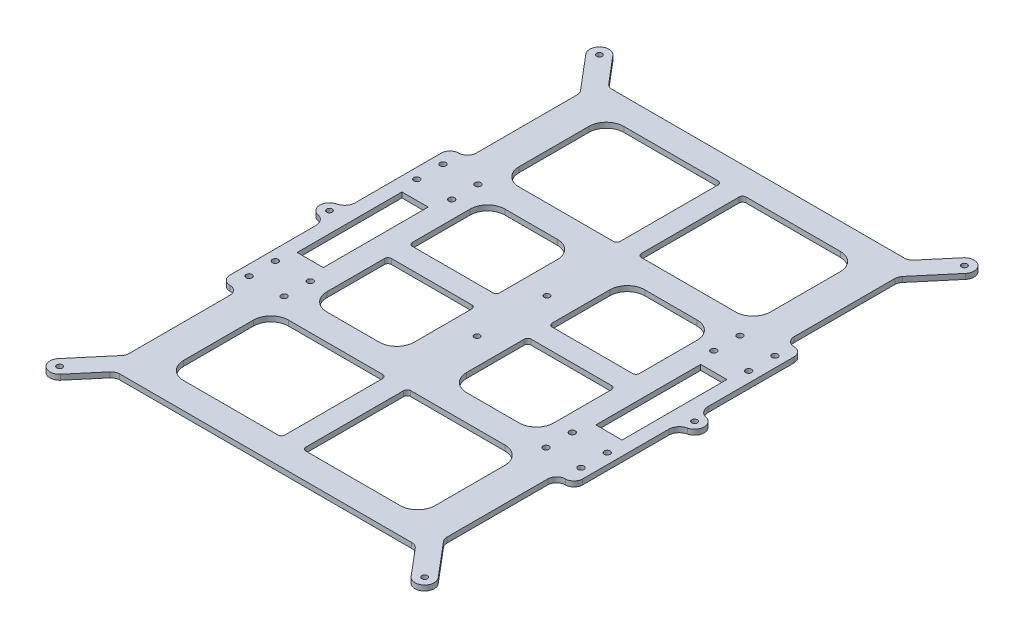
SolidWorks part; units mm, degrees
material "Aleación 1060"
ref_plane "Alzado" through (0, 0, 0) normal (0, 0, 1) x (1, 0, 0)
ref_plane "Planta" through (0, 0, 0) normal (0, 1, 0) x (1, 0, 0)
ref_plane "Vista lateral" through (0, 0, 0) normal (1, 0, 0) x (0, 0, -1)
sketch "Croquis1" plane through (0, 0, 0) normal (0, 1, 0) x (1, 0, 0)
  line L0 (110, 320) -> (110, 0) construction
  line L1 (0, 0) -> (220, 0)
  line L2 (0, 0) -> (0, 320)
  line L3 (0, 320) -> (220, 320)
  line L4 (220, 0) -> (220, 320)
  line L5 (0, 160) -> (220, 160) construction
  line L6 (19, 320) -> (19, 0) construction
  line L7 (31, 320) -> (31, 0) construction
  line L8 (189, 320) -> (189, 0) construction
  line L9 (201, 320) -> (201, 0) construction
  line L10 (195, 320) -> (195, 0) construction
  line L11 (25, 320) -> (25, 0) construction
  line L12 (5.5, 314.5) -> (5.5, 160) construction
  circle A7 centre (35, 215.5) radius 1.7
  circle A8 centre (35, 200.5) radius 1.7
  circle A10 centre (35, 119.5) radius 1.7
  circle A13 centre (35, 104.5) radius 1.7
  circle A14 centre (5.5, 314.5) radius 1.6
  circle A15 centre (214.5, 314.5) radius 1.6
  circle A16 centre (214.5, 5.5) radius 1.6
  circle A17 centre (5.5, 5.5) radius 1.6
  circle A18 centre (15, 200.5) radius 1.7
  circle A19 centre (15, 215.5) radius 1.7
  circle A20 centre (15, 104.5) radius 1.7
  circle A21 centre (15, 119.5) radius 1.7
  circle A22 centre (110, 180) radius 1.6
  circle A23 centre (110, 140) radius 1.6
  circle A32 centre (5.5, 160) radius 1.6
  circle A37 centre (214.5, 160) radius 1.6
  circle A38 centre (185, 104.5) radius 1.7
  circle A39 centre (185, 119.5) radius 1.7
  circle A40 centre (205, 119.5) radius 1.7
  circle A41 centre (205, 104.5) radius 1.7
  circle A42 centre (185, 215.5) radius 1.7
  circle A43 centre (185, 200.5) radius 1.7
  circle A44 centre (205, 200.5) radius 1.7
  circle A45 centre (205, 215.5) radius 1.7
  dimension "D13" = 6
  dimension "D14" = 3.4
  dimension "D17" = 3.2
  dimension "D23" = 3.2
  dimension "D18" = 20
  dimension "D1" = 320
  dimension "D2" = 220
  dimension "D3" = 12
  dimension "D4" = 12
  dimension "D5" = 158
  dimension "D6" = 19
  dimension "D7" = 6
  dimension "D15" = 10
  dimension "D16" = 15
  dimension "D20" = 10
  dimension "D21" = 104.5
  dimension "D24" = 5.5
  dimension "D25" = 5.5
extrude "Saliente-Extruir1" add sketch "Croquis1" along normal blind 3
sketch "Croquis2" plane through (0, 3, 0) normal (0, 1, 0) x (1, 0, 0)
  line L0 (220, 160) -> (0, 160) construction
  line L2 (9, 9) -> (211, 9) construction
  line L3 (220, 0) -> (220, 320) construction
  line L4 (9, 148.775) -> (9, 94.5)
  line L5 (110, 320) -> (110, 0) construction
  line L6 (220, 320) -> (0, 320) construction
  line L7 (0, 0) -> (220, 0) construction
  line L8 (9, 9) -> (211, 9)
  line L9 (211, 9) -> (211, 311)
  line L10 (211, 311) -> (9, 311)
  line L11 (9, 311) -> (9, 9)
  line L15 (9, 225.5) -> (9, 171.225)
  line L16 (9, 225.5) -> (19, 225.5)
  line L18 (19, 94.5) -> (9, 94.5)
  line L19 (19, 94.5) -> (19, 30)
  line L20 (24.1066, 19) -> (195.8934, 19)
  line L21 (210.2988, 1.9504) -> (195.8934, 19)
  line L22 (1.2988, 9.0496) -> (19, 30)
  line L23 (9.7012, 1.9504) -> (24.1066, 19)
  line L24 (9, 148.775) -> (9, 9) construction
  line L25 (19, 148.775) -> (19, 19) construction
  line L26 (19, 19) -> (201, 19) construction
  line L27 (211, 9) -> (211, 311) construction
  line L28 (19, 225.5) -> (19, 290)
  line L29 (24.1066, 301) -> (195.8934, 301)
  line L30 (1.2988, 310.9504) -> (19, 290)
  line L31 (9.7012, 318.0496) -> (24.1066, 301)
  line L32 (0, 320) -> (0, 0) construction
  line L33 (218.7012, 9.0496) -> (201, 30)
  line L34 (201, 19) -> (201, 311) construction
  line L35 (201, 94.5) -> (201, 30)
  line L36 (201, 94.5) -> (211, 94.5)
  line L37 (211, 148.775) -> (211, 94.5)
  line L38 (211, 225.5) -> (211, 171.225)
  line L39 (211, 225.5) -> (201, 225.5)
  line L40 (201, 225.5) -> (201, 290)
  line L41 (218.7012, 310.9504) -> (201, 290)
  line L42 (210.2988, 318.0496) -> (195.8934, 301)
  line L43 (182, 276) -> (182, 236)
  line L44 (102, 286) -> (48, 286)
  line L46 (102, 226) -> (48, 226)
  line L47 (38, 276) -> (38, 236)
  line L48 (118, 226) -> (172, 226)
  line L52 (104, 284) -> (104, 228)
  line L53 (116, 284) -> (116, 228)
  line L54 (118, 286) -> (172, 286)
  line L55 (102, 94) -> (48, 94)
  line L56 (38, 44) -> (38, 84)
  line L57 (102, 34) -> (48, 34)
  line L58 (104, 36) -> (104, 92)
  line L59 (116, 36) -> (116, 92)
  line L60 (118, 34) -> (172, 34)
  line L61 (182, 44) -> (182, 84)
  line L62 (118, 94) -> (172, 94)
  line L63 (45, 152) -> (45, 119)
  line L64 (93, 166) -> (47, 166)
  line L65 (95, 168) -> (95, 201)
  line L66 (85, 211) -> (55, 211)
  line L67 (45, 168) -> (45, 201)
  line L68 (85, 109) -> (55, 109)
  line L69 (95, 152) -> (95, 119)
  line L70 (93, 154) -> (47, 154)
  line L71 (135, 109) -> (165, 109)
  line L72 (175, 152) -> (175, 119)
  line L73 (125, 152) -> (125, 119)
  line L74 (127, 154) -> (173, 154)
  line L75 (127, 166) -> (173, 166)
  line L76 (175, 168) -> (175, 201)
  line L77 (135, 211) -> (165, 211)
  line L78 (125, 168) -> (125, 201)
  arc A2 (1.2988, 9.0496) -> (9.7012, 1.9504) centre (5.5, 5.5) ccw
  arc A3 (4.3043, 165.3685) -> (4.3043, 154.6315) centre (5.5, 160) ccw
  arc A4 (9, 148.775) -> (4.3043, 154.6315) centre (3, 148.775) ccw
  arc A5 (9, 171.225) -> (4.3043, 165.3685) centre (3, 171.225) cw
  circle A6 centre (35, 215.5) radius 1.7 construction
  circle A7 centre (35, 104.5) radius 1.7 construction
  arc A8 (48, 226) -> (38, 236) centre (48, 236) cw
  arc A10 (1.2988, 310.9504) -> (9.7012, 318.0496) centre (5.5, 314.5) cw
  arc A11 (218.7012, 9.0496) -> (210.2988, 1.9504) centre (214.5, 5.5) cw
  arc A12 (211, 148.775) -> (215.6957, 154.6315) centre (217, 148.775) cw
  arc A13 (215.6957, 165.3685) -> (215.6957, 154.6315) centre (214.5, 160) cw
  arc A14 (211, 171.225) -> (215.6957, 165.3685) centre (217, 171.225) ccw
  arc A15 (218.7012, 310.9504) -> (210.2988, 318.0496) centre (214.5, 314.5) ccw
  arc A16 (48, 286) -> (38, 276) centre (48, 276) ccw
  arc A17 (172, 226) -> (182, 236) centre (172, 236) ccw
  arc A18 (172, 286) -> (182, 276) centre (172, 276) cw
  arc A19 (48, 94) -> (38, 84) centre (48, 84) ccw
  arc A20 (48, 34) -> (38, 44) centre (48, 44) cw
  arc A21 (172, 34) -> (182, 44) centre (172, 44) ccw
  arc A22 (172, 94) -> (182, 84) centre (172, 84) cw
  arc A23 (102, 226) -> (104, 228) centre (102, 228) ccw
  arc A24 (102, 286) -> (104, 284) centre (102, 284) cw
  arc A25 (116, 284) -> (118, 286) centre (118, 284) cw
  arc A26 (118, 226) -> (116, 228) centre (118, 228) cw
  arc A27 (116, 92) -> (118, 94) centre (118, 92) cw
  arc A28 (116, 36) -> (118, 34) centre (118, 36) ccw
  arc A29 (102, 34) -> (104, 36) centre (102, 36) ccw
  arc A30 (102, 94) -> (104, 92) centre (102, 92) cw
  arc A31 (95, 201) -> (85, 211) centre (85, 201) ccw
  arc A32 (55, 211) -> (45, 201) centre (55, 201) ccw
  arc A33 (55, 109) -> (45, 119) centre (55, 119) cw
  arc A34 (95, 119) -> (85, 109) centre (85, 119) cw
  arc A35 (165, 109) -> (175, 119) centre (165, 119) ccw
  arc A36 (125, 119) -> (135, 109) centre (135, 119) ccw
  arc A37 (165, 211) -> (175, 201) centre (165, 201) cw
  arc A38 (125, 201) -> (135, 211) centre (135, 201) cw
  arc A39 (127, 166) -> (125, 168) centre (127, 168) cw
  arc A40 (173, 166) -> (175, 168) centre (173, 168) ccw
  arc A41 (175, 152) -> (173, 154) centre (173, 152) ccw
  arc A42 (125, 152) -> (127, 154) centre (127, 152) cw
  arc A43 (45, 152) -> (47, 154) centre (47, 152) cw
  arc A44 (95, 152) -> (93, 154) centre (93, 152) ccw
  arc A45 (93, 166) -> (95, 168) centre (93, 168) ccw
  arc A46 (47, 166) -> (45, 168) centre (47, 168) cw
  point P28 (110, 19)
  point P71 (110, 301)
  point P76 (38, 226)
  point P79 (38, 286)
  point P106 (104, 226)
  point P109 (104, 286)
  point P112 (116, 286)
  point P115 (116, 226)
  point P118 (116, 94)
  point P121 (116, 34)
  point P124 (104, 34)
  point P127 (104, 94)
  point P137 (95, 211)
  point P140 (45, 211)
  point P167 (125, 166)
  point P170 (175, 166)
  point P173 (175, 154)
  point P176 (125, 154)
  point P179 (45, 154)
  point P182 (95, 154)
  point P185 (95, 166)
  point P188 (45, 166)
  dimension "D2" = 11
  dimension "D3" = 11
  dimension "D4" = 6
  dimension "D5" = 10
  dimension "D6" = 10
  dimension "D7" = 60
  dimension "D12" = 10
  dimension "D14" = 2
  dimension "D19" = 10
  dimension "D20" = 2
  dimension "D9" = 30
  dimension "D10" = 15
  dimension "D8" = 19
  dimension "D11" = 38
  dimension "D13" = 6
  dimension "D15" = 6
  dimension "D16" = 15
  dimension "D17" = 50
  dimension "D18" = 45
  dimension "D1" = 9
extrude "Cortar-Extruir1" cut sketch "Croquis2" against normal up to surface (3 mm away) flip side to cut up to face at (5.5, 0, -158.4)
fillet "Redondeo1" radius 5 16 edges at (211, 1.5, -225.5) (211, 1.5, -94.5) (9, 1.5, -225.5) (9, 1.5, -94.5) (24.1066, 1.5, -301) (195.8934, 1.5, -301) (201, 1.5, -290) (201, 1.5, -225.5) (201, 1.5, -94.5) (201, 1.5, -30) (195.8934, 1.5, -19) (24.1066, 1.5, -19) (19, 1.5, -30) (19, 1.5, -94.5) (19, 1.5, -290) (19, 1.5, -225.5)
sketch "Croquis4" plane through (0, 3, 0) normal (0, 1, 0) x (1, 0, 0)
  line L0 (9, 220.5) -> (9, 171.225) construction
  line L1 (17, 190) -> (32, 190)
  line L2 (17, 190) -> (17, 130)
  line L3 (17, 130) -> (32, 130)
  line L4 (32, 190) -> (32, 130)
  line L5 (193.5722, 301) -> (26.4278, 301) construction
  line L6 (193.5722, 301) -> (26.4278, 301) construction
  line L7 (110, 301) -> (110, 6.1719) construction
  line L8 (188, 190) -> (188, 130)
  line L9 (203, 130) -> (188, 130)
  line L10 (203, 190) -> (203, 130)
  line L11 (203, 190) -> (188, 190)
  circle A0 centre (5.5, 160) radius 1.6 construction
  dimension "D3" = 30
  dimension "D1" = 15
  dimension "D2" = 60
  dimension "D4" = 8
extrude "Cortar-Extruir3" cut sketch "Croquis4" against normal up to surface (3 mm away) contours L4 L1 L2 L3 | L10 L11 L8 L9 region at (24.5, 3, -160) region at (195.5, 3, -160) up to face at (70, 0, -186.9142)
